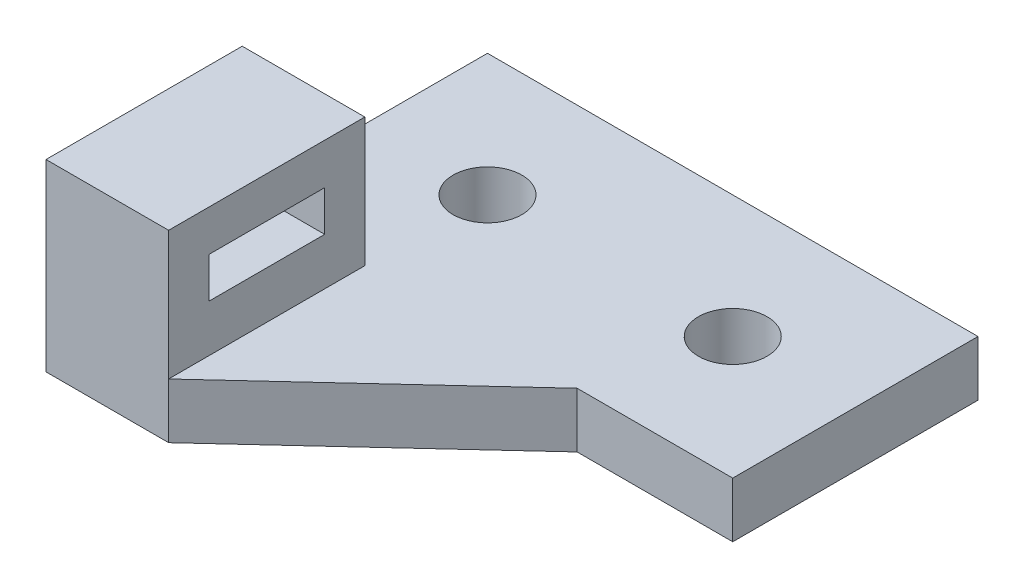
SolidWorks part; units mm, degrees
ref_plane "Front Plane" through (0, 0, 0) normal (0, 0, 1) x (1, 0, 0)
ref_plane "Top Plane" through (0, 0, 0) normal (0, 1, 0) x (1, 0, 0)
ref_plane "Right Plane" through (0, 0, 0) normal (1, 0, 0) x (0, 0, -1)
sketch "Sketch1" plane through (0, 0, 0) normal (0, 1, 0) x (1, 0, 0)
  line L0 (-10, 10) -> (30, 10)
  line L1 (30, 10) -> (30, -10)
  line L2 (30, -10) -> (0, -10)
  line L3 (0, -10) -> (0, -26)
  line L4 (0, -26) -> (-10, -26)
  line L7 (-10, -26) -> (-10, 10)
  line L8 (-26.7442, -18) -> (27.2503, -18) construction
  line L9 (30, 0) -> (-16.2534, 0) construction
  line L10 (0, -26) -> (17.3123, -10)
  line L11 (0, -26) -> (-10, -26)
  line L12 (0, -26) -> (0, -10)
  line L13 (0, -10) -> (-10, -10)
  line L14 (-10, -26) -> (-10, -10)
  circle A0 centre (0, 0) radius 2.8
  circle A1 centre (20, 0) radius 2.8
  point P18 (0, -26.7358)
  point P21 (0, -18)
  dimension "D2" = 5.6
  dimension "D1" = 20
  dimension "D3" = 18
  dimension "D4" = 10
  dimension "D5" = 10
  dimension "D6" = 10
extrude "Boss-Extrude1" add sketch "Sketch1" along normal blind 4.5 contours L13 L2 L1 L0 L7 A1 A0 | L3 L10 L2 region at (10, 0, 0) region at (5.7708, 0, 15.3333)
extrude "Boss-Extrude2" add sketch "Sketch1<3>" along normal blind 15 contours L3 L13 L7 L4 region at (-5, 0, 18)
sketch "Sketch1<3>" plane through (0, 0, 0) normal (0, 1, 0) x (1, 0, 0) same geometry as "Sketch1"
ref_plane "Plane1" through (0, 0, 18) normal (0, 0, 1) x (1, 0, 0)
ref_plane "Plane2" through (0, 10, 0) normal (0, 1, 0) x (1, 0, 0)
sketch "Sketch2" plane through (0, 0, 0) normal (1, 0, 0) x (0, 0, -1)
  line L0 (-18, 29.697) -> (-18, -29.697) construction
  line L1 (-22.725, 8.35) -> (-13.275, 8.35)
  line L2 (-22.725, 8.35) -> (-22.725, 11.65)
  line L3 (-22.725, 11.65) -> (-13.275, 11.65)
  line L4 (-13.275, 8.35) -> (-13.275, 11.65)
  line L5 (-22.725, 8.35) -> (-13.275, 11.65) construction
  line L6 (-22.725, 11.65) -> (-13.275, 8.35) construction
  line L7 (19.8, 10) -> (-19.8, 10) construction
  point P0 (-18, 10)
  point P5 (-18.4294, 9.7025)
  point P6 (0, 0)
  point P9 (0, 0)
  point P10 (0, 0)
  dimension "D1" = 9.45
  dimension "D2" = 3.3
extrude "Cut-Extrude1" cut sketch "Sketch2" against normal through all contours L3 L4 L1 L2
equation "\"D6@Sketch1\"=\"D5@Sketch1\""
